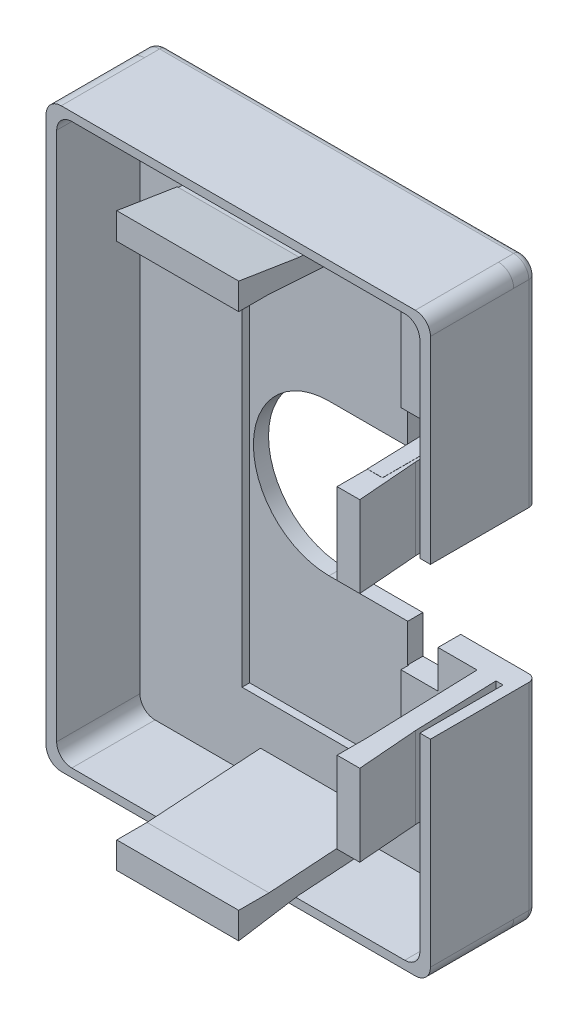
SolidWorks part; units mm, degrees
material "PLA"
ref_plane "Alzado" through (0, 0, 0) normal (0, 0, 1) x (1, 0, 0)
ref_plane "Planta" through (0, 0, 0) normal (0, 1, 0) x (1, 0, 0)
ref_plane "Vista lateral" through (0, 0, 0) normal (1, 0, 0) x (0, 0, -1)
sketch "Croquis1" plane through (0, 0, 0) normal (0, 0, 1) x (1, 0, 0)
  line L1 (25.4, 38.1) -> (-25.4, 38.1)
  line L2 (25.4, 38.1) -> (25.4, -38.1)
  line L3 (25.4, -38.1) -> (-25.4, -38.1)
  line L4 (-25.4, 38.1) -> (-25.4, -38.1)
  line L5 (25.4, 38.1) -> (-25.4, -38.1) construction
  line L6 (25.4, -38.1) -> (-25.4, 38.1) construction
  point P0 (0, 0)
  dimension "D1" = 76.2
  dimension "D2" = 50.8
extrude "Saliente-Extruir1" add sketch "Croquis1" along normal blind 18
sketch "Croquis2" plane through (0, 0, 18) normal (0, 0, 1) x (1, 0, 0)
  line L0 (25.4, 38.1) -> (-25.4, 38.1) construction
  line L1 (-23.06, 35.76) -> (23.06, 35.76)
  line L2 (-23.06, 35.76) -> (-23.06, -35.76)
  line L3 (-23.06, -35.76) -> (23.06, -35.76)
  line L4 (23.06, 35.76) -> (23.06, -35.76)
  line L5 (-25.4, -38.1) -> (25.4, -38.1) construction
  line L6 (-25.4, 38.1) -> (-25.4, -38.1) construction
  line L7 (25.4, -38.1) -> (25.4, 38.1) construction
  line L9 (-25.4, 38.1) -> (25.4, 38.1)
  line L10 (-25.4, 38.1) -> (-25.4, -38.1)
  line L11 (-25.4, -38.1) -> (25.4, -38.1)
  line L12 (25.4, 38.1) -> (25.4, -38.1)
  line L13 (-19.4, 32.1) -> (19.4, 32.1)
  line L14 (-19.4, 32.1) -> (-19.4, -32.1)
  line L15 (-19.4, -32.1) -> (19.4, -32.1)
  line L16 (19.4, 32.1) -> (19.4, -32.1)
  line M9 (-25.4, 38.1) -> (-25.4, -38.1)
  line M10 (-25.4, -38.1) -> (25.4, -38.1)
  line M11 (25.4, -38.1) -> (25.4, 38.1)
  line M12 (25.4, 38.1) -> (-25.4, 38.1)
  dimension "D1" = 2.34
  dimension "D2" = 2.34
  dimension "D3" = 2.34
  dimension "D4" = 2.34
  dimension "D5" = 6
  dimension "D6" = 6
  dimension "D7" = 6
  dimension "D8" = 6
extrude "Cortar-Extruir1" cut sketch "Croquis2" against normal blind 15 contours L1 L4 L3 L2 M12 M9 M10 M11 | L16 L13 L14 L15 region at (0, 37.1842, 18) region at (0, 0, 18)
sketch "Croquis3" plane through (0, 0, 18) normal (0, 0, 1) x (1, 0, 0)
  line L0 (-23.06, 35.76) -> (-23.06, -35.76) construction
  line L1 (-23.06, 22.1) -> (-19.4, 22.1)
  line L2 (-23.06, 22.1) -> (-23.06, -22.1)
  line L3 (-23.06, -22.1) -> (-19.4, -22.1)
  line L4 (-19.4, 22.1) -> (-19.4, -22.1)
  line L5 (-19.4, 32.1) -> (-19.4, -32.1) construction
  line L6 (-19.4, -32.1) -> (19.4, -32.1) construction
  line L7 (-9.4, -32.1) -> (9.3837, -32.1)
  line L8 (-9.4, -32.1) -> (-9.4, -35.76)
  line L9 (-9.4, -35.76) -> (9.3837, -35.76)
  line L10 (9.3837, -32.1) -> (9.3837, -35.76)
  line L11 (-23.06, -35.76) -> (23.06, -35.76) construction
  line L12 (19.4, 32.1) -> (19.4, -32.1) construction
  line L13 (19.4, -22.1) -> (23.06, -22.1)
  line L14 (19.4, -22.1) -> (19.4, 22.1)
  line L15 (19.4, 22.1) -> (23.06, 22.1)
  line L16 (23.06, -22.1) -> (23.06, 22.1)
  line L17 (23.06, 35.76) -> (23.06, -35.76) construction
  line L18 (-23.06, 35.76) -> (23.06, 35.76) construction
  line L19 (-9.4, 35.76) -> (9.4, 35.76)
  line L20 (-9.4, 35.76) -> (-9.4, 32.1)
  line L21 (-9.4, 32.1) -> (9.4, 32.1)
  line L22 (9.4, 35.76) -> (9.4, 32.1)
  line L23 (-19.4, 32.1) -> (19.4, 32.1) construction
  line L24 (-19.4, 32.1) -> (-19.4, -32.1) construction
  line L25 (19.4, 32.1) -> (19.4, -32.1) construction
  dimension "D1" = 10
  dimension "D2" = 10
  dimension "D3" = 10
  dimension "D4" = 10
  dimension "D5" = 10
  dimension "D6" = 10
  dimension "D7" = 10
extrude "Cortar-Extruir2" [suppressed] cut sketch "Croquis3" against normal blind 7
fillet "Redondeo1" [suppressed] radius 2
fillet "Redondeo2" [suppressed] radius 1
sketch "Croquis5" [suppressed] plane through (0, -38.1, 0) normal (0, -1, 0) x (1, 0, 0)
  line L0 (-23.4, 3) -> (23.4, 3) construction
  line L1 (-3, 3) -> (3, 3)
  line L2 (-3, 3) -> (-3, 1.5)
  line L3 (-3, 1.5) -> (3, 1.5)
  line L4 (3, 3) -> (3, 1.5)
  line L5 (0, 1) -> (0, 3) construction
  line L6 (-23.4, 1) -> (23.4, 1) construction
  dimension "D1" = 3
  dimension "D2" = 3
  dimension "D3" = 1.5
extrude "Cortar-Extruir4" [suppressed] cut sketch "Croquis5" against normal blind 6
sketch "Croquis6" plane through (0, 0, 18) normal (0, 0, 1) x (1, 0, 0)
  line L0 (-23.06, 35.76) -> (-8.06, 35.76)
  line L1 (-23.06, 35.76) -> (23.06, 35.76) construction
  line L2 (-8.06, 35.76) -> (-8.06, 32.1)
  line L3 (-19.4, 32.1) -> (19.4, 32.1) construction
  line L4 (-8.06, 32.1) -> (-19.4, 32.1)
  line L5 (-19.4, 32.1) -> (-19.4, 20.76)
  line L6 (-19.4, 32.1) -> (-19.4, -32.1) construction
  line L7 (-19.4, 20.76) -> (-23.06, 20.76)
  line L8 (-23.06, 35.76) -> (-23.06, -35.76) construction
  line L9 (-23.06, 20.76) -> (-23.06, 35.76)
  line L10 (23.06, 35.76) -> (8.06, 35.76)
  line L11 (-23.06, 35.76) -> (23.06, 35.76) construction
  line L12 (8.06, 35.76) -> (8.06, 32.1)
  line L13 (8.06, 32.1) -> (19.4, 32.1)
  line L14 (19.4, 32.1) -> (19.4, -32.1) construction
  line L15 (19.4, 32.1) -> (19.4, -32.1) construction
  line L16 (19.4, 32.1) -> (19.4, 20.76)
  line L17 (19.4, 20.76) -> (23.06, 20.76)
  line L18 (23.06, 35.76) -> (23.06, -35.76) construction
  line L19 (23.06, 20.76) -> (23.06, 35.76)
  line L20 (-23.06, -35.76) -> (-23.06, -20.76)
  line L21 (-23.06, 35.76) -> (-23.06, -35.76) construction
  line L22 (-23.06, -20.76) -> (-19.4, -20.76)
  line L23 (-19.4, 32.1) -> (-19.4, -32.1) construction
  line L24 (-19.4, -20.76) -> (-19.4, -32.1)
  line L25 (-19.4, -32.1) -> (-8.06, -32.1)
  line L26 (-19.4, -32.1) -> (19.4, -32.1) construction
  line L27 (-8.06, -32.1) -> (-8.06, -35.76)
  line L28 (-23.06, -35.76) -> (23.06, -35.76) construction
  line L29 (-8.06, -35.76) -> (-23.06, -35.76)
  line L30 (23.06, -35.76) -> (8.06, -35.76)
  line L31 (-23.06, -35.76) -> (23.06, -35.76) construction
  line L32 (8.06, -35.76) -> (8.06, -32.1)
  line L33 (-19.4, -32.1) -> (19.4, -32.1) construction
  line L34 (8.06, -32.1) -> (19.4, -32.1)
  line L35 (19.4, -32.1) -> (19.4, -20.76)
  line L36 (19.4, -20.76) -> (23.06, -20.76)
  line L37 (23.06, 35.76) -> (23.06, -35.76) construction
  line L38 (23.06, -20.76) -> (23.06, -35.76)
  dimension "D1" = 15
  dimension "D2" = 15
  dimension "D3" = 15
  dimension "D4" = 15
  dimension "D5" = 15
  dimension "D6" = 15
  dimension "D7" = 15
  dimension "D8" = 15
extrude "Cortar-Extruir8" cut sketch "Croquis6" against normal blind 15
sketch "Croquis10" plane through (0, -20.76, 0) normal (0, -1, 0) x (-1, 0, 0)
  line L0 (23.06, -18) -> (23.56, -18)
  line L1 (23.56, -18) -> (23.06, -3)
  line L2 (23.06, -3) -> (23.06, -18)
  line L3 (-23.06, -18) -> (-23.56, -18)
  line L4 (-23.56, -18) -> (-23.06, -3)
  line L5 (-23.06, -3) -> (-23.06, -18)
  dimension "D1" = 0.5
  dimension "D2" = 0.5
extrude "Saliente-Extruir3" add sketch "Croquis10" against normal blind 41.5
sketch "Croquis11" plane through (0, -20.76, 0) normal (0, -1, 0) x (1, 0, 0)
  line L0 (-19.4, 18) -> (-21.06, 18)
  line L1 (-19.4, 18) -> (-23.56, 18) construction
  line L2 (-21.06, 18) -> (-20.56, 3)
  line L3 (-19.4, 3) -> (-23.06, 3) construction
  line L4 (-20.56, 3) -> (-19.4, 3)
  line L5 (-19.4, 18) -> (-19.4, 3)
  dimension "D1" = 2.5
  dimension "D2" = 1.16
extrude "Cortar-Extruir9" cut sketch "Croquis11" against normal blind 51.5
sketch "Croquis12" plane through (0, -20.76, 0) normal (0, -1, 0) x (1, 0, 0)
  line L0 (19.4, 18) -> (19.4, 3)
  line L1 (19.4, 3) -> (20.56, 3)
  line L2 (23.06, 3) -> (19.4, 3) construction
  line L3 (20.56, 3) -> (21.06, 18)
  line L4 (23.56, 18) -> (19.4, 18) construction
  line L5 (21.06, 18) -> (19.4, 18)
  dimension "D1" = 2.5
  dimension "D2" = 1.16
extrude "Cortar-Extruir10" cut sketch "Croquis12" against normal blind 51.5
sketch "Croquis13" plane through (8.06, 0, 0) normal (1, 0, 0) x (0, 0, -1)
  line L0 (-18, -35.76) -> (-18, -36.76)
  line L1 (-18, -36.76) -> (-3, -35.76)
  line L2 (-3, -35.76) -> (-18, -35.76)
  line L3 (-18, 35.76) -> (-18, 36.76)
  line L4 (-18, 36.76) -> (-3, 35.76)
  line L5 (-3, 35.76) -> (-18, 35.76)
  dimension "D1" = 1
  dimension "D2" = 1
extrude "Saliente-Extruir4" add sketch "Croquis13" against normal blind 16
sketch "Croquis14" plane through (8.06, 0, 0) normal (1, 0, 0) x (0, 0, -1)
  line L0 (-3, -32.1) -> (-18, -32.1)
  line L1 (-18, -32.1) -> (-18, -34.26)
  line L2 (-18, -32.1) -> (-18, -36.76) construction
  line L3 (-18, -34.26) -> (-3, -33.26)
  line L4 (-3, -32.1) -> (-3, -35.76) construction
  line L5 (-3, -33.26) -> (-3, -32.1)
  line L6 (-18, 32.1) -> (-18, 34.26)
  line L7 (-18, 36.76) -> (-18, 32.1) construction
  line L8 (-18, 34.26) -> (-3, 33.26)
  line L9 (-3, 35.76) -> (-3, 32.1) construction
  line L10 (-3, 33.26) -> (-3, 32.1)
  line L11 (-3, 32.1) -> (-18, 32.1)
  dimension "D1" = 2.5
  dimension "D2" = 1.16
  dimension "D3" = 2.5
  dimension "D4" = 1.16
extrude "Cortar-Extruir11" cut sketch "Croquis14" against normal blind 16.5
fillet "Redondeo3" radius 2 4 edges at (25.4, 38.1, 1.5) (-25.4, 38.1, 1.5) (-25.4, -38.1, 1.5) (25.4, -38.1, 1.5)
fillet "Redondeo4" radius 1 8 edges at (-24.8142, 37.5142, 0) (-25.4, 0, 0) (-24.8142, -37.5142, 0) (0, -38.1, 0) (24.8142, -37.5142, 0) (25.4, 0, 0) (24.8142, 37.5142, 0) (0, 38.1, 0)
sketch "Croquis15" plane through (0, 0, 18) normal (0, 0, 1) x (1, 0, 0)
  line L0 (-23.56, -0.01) -> (23.56, -0.01) construction
  line L1 (-23.56, 20.74) -> (-23.56, -20.76) construction
  line L2 (23.56, 20.74) -> (23.56, -20.76) construction
  line L4 (-23.56, 4.99) -> (23.56, 4.99)
  line L5 (-23.56, 4.99) -> (-23.56, -5.01)
  line L6 (-23.56, -5.01) -> (23.56, -5.01)
  line L7 (23.56, 4.99) -> (23.56, -5.01)
  dimension "D1" = 5
  dimension "D2" = 5
extrude "Cortar-Extruir12" cut sketch "Croquis15" against normal blind 15
sketch "Croquis16" plane through (0, -38.1, 0) normal (0, -1, 0) x (1, 0, 0)
  line L0 (-23.4, 3) -> (23.4, 3) construction
  line L1 (-4, 3) -> (4, 3)
  line L2 (-4, 3) -> (-4, 1.5)
  line L3 (-4, 1.5) -> (4, 1.5)
  line L4 (4, 3) -> (4, 1.5)
  dimension "D1" = 1.5
  dimension "D2" = 8
  dimension "D3" = 4
extrude "Cortar-Extruir13" [suppressed] cut sketch "Croquis16" against normal blind 2
sketch "Croquis17" plane through (0, 0, 3) normal (0, 0, 1) x (1, 0, 0)
  line L0 (-25.4, 36.1) -> (-25.4, -36.1) construction
  line L1 (-23.4, -38.1) -> (23.4, -38.1) construction
  circle A0 centre (-13.4, -23.1) radius 3
  dimension "D2" = 6
  dimension "D1" = 12
  dimension "D3" = 15
extrude "Cortar-Extruir14" [suppressed] cut sketch "Croquis17" against normal blind 10
sketch "Croquis18" plane through (0, 0, 3) normal (0, 0, 1) x (1, 0, 0)
  line L0 (0, 10) -> (25.4, 10)
  line L1 (25.4, -36.1) -> (25.4, 36.1) construction
  line L2 (0, -10) -> (25.4, -10)
  line L3 (25.4, -10) -> (25.4, 10)
  circle A0 centre (0, 0) radius 10
  line M7 (25.4, -36.1) -> (25.4, 36.1)
  line M14 (23.06, 20.74) -> (23.06, 4.99)
  line M15 (23.06, 4.99) -> (20.56, 4.99)
  line M16 (20.56, 4.99) -> (20.56, 20.76)
  line M28 (20.56, -20.76) -> (20.56, -5.01)
  line M29 (20.56, -5.01) -> (23.06, -5.01)
  line M30 (23.06, -5.01) -> (23.06, -20.76)
  dimension "D1" = 20
extrude "Cortar-Extruir16" cut sketch "Croquis18" against normal through all and the other way through all contours A0 | L2 M28 M30 M29 | L0 M16 M15 M14 | A0 L2 L0 M28 M29 M30 M7 M14 M15 M16 region at (16.0766, -0.0008, 3) region at (0, 0, 3) region at (21.81, 7.495, 3) region at (21.81, -7.505, 3)
sketch "Croquis19" plane through (0, 0, 3) normal (0, 0, 1) x (1, 0, 0)
  line L0 (0, 10) -> (20.56, 10) construction
  line L1 (10.4, 10) -> (15.4, 10)
  line L2 (10.4, 10) -> (10.4, 15)
  line L3 (10.4, 15) -> (15.4, 15)
  line L4 (15.4, 10) -> (15.4, 15)
  line L5 (0, -10) -> (20.56, -10) construction
  line L6 (10.4, -10) -> (15.4, -10)
  line L7 (10.4, -10) -> (10.4, -15)
  line L8 (10.4, -15) -> (15.4, -15)
  line L9 (15.4, -10) -> (15.4, -15)
  dimension "D1" = 5
  dimension "D2" = 5
  dimension "D3" = 5
  dimension "D4" = 5
  dimension "D5" = 10
  dimension "D6" = 10
extrude "Cortar-Extruir17" cut sketch "Croquis19" against normal through all
sketch "Croquis20" plane through (0, 0, 3) normal (0, 0, 1) x (1, 0, 0)
  line L1 (-25.4, 38.1) -> (25.4, 38.1)
  line L2 (-25.4, 38.1) -> (-25.4, -38.1)
  line L3 (-25.4, -38.1) -> (25.4, -38.1)
  line L4 (25.4, 38.1) -> (25.4, -38.1)
  line L5 (-25.4, 38.1) -> (25.4, -38.1) construction
  line L6 (-25.4, -38.1) -> (25.4, 38.1) construction
  line L7 (24, 37) -> (-24, 37)
  line L8 (24, 37) -> (24, -37)
  line L9 (24, -37) -> (-24, -37)
  line L10 (-24, 37) -> (-24, -37)
  line L11 (24, 37) -> (-24, -37) construction
  line L12 (24, -37) -> (-24, 37) construction
  point P0 (0, 0)
  point P6 (0, 0)
  dimension "D1" = 76.2
  dimension "D2" = 50.8
  dimension "D3" = 48
  dimension "D4" = 74
extrude "Saliente-Extruir5" add sketch "Croquis20" along normal blind 11 contours L2 L1 L4 L3 | L8 L7 L10 L9
sketch "Croquis21" plane through (25.4, 0, 0) normal (1, 0, 0) x (0, 0, -1)
  line L1 (-3, 10) -> (-28, 10)
  line L2 (-3, 10) -> (-3, -10)
  line L3 (-3, -10) -> (-28, -10)
  line L4 (-28, 10) -> (-28, -10)
  dimension "D1" = 20
  dimension "D2" = 25
extrude "Cortar-Extruir18" cut sketch "Croquis21" against normal blind 10
sketch "Croquis22" plane through (0, 0, 3) normal (0, 0, 1) x (1, 0, 0)
  line L1 (10.5, 27.5) -> (-10.5, 27.5)
  line L2 (10.5, 27.5) -> (10.5, -27.5)
  line L3 (10.5, -27.5) -> (-10.5, -27.5)
  line L4 (-10.5, 27.5) -> (-10.5, -27.5)
  line L5 (10.5, 27.5) -> (-10.5, -27.5) construction
  line L6 (10.5, -27.5) -> (-10.5, 27.5) construction
  point P0 (0, 0)
  dimension "D1" = 21
  dimension "D2" = 55
extrude "Cortar-Extruir19" cut sketch "Croquis22" against normal blind 1
fillet "Redondeo5" radius 2 8 edges at (25.4, -38.1, 8.5) (-25.4, -38.1, 8.5) (-25.4, 38.1, 8.5) (25.4, 38.1, 8.5) (-24, 37, 8.5) (-24, -37, 8.5) (24, -37, 8.5) (24, 37, 8.5)
sketch "Croquis23" plane through (0, 0, 18) normal (0, 0, 1) x (1, 0, 0)
  line L0 (-23.56, 20.74) -> (-23.56, 4.99) construction
  line L5 (-21.06, 20.76) -> (-23.56, 20.76)
  line L6 (-21.06, 20.76) -> (-21.06, 5.0051)
  line L7 (-21.06, 5.0051) -> (-23.56, 5.0051)
  line L8 (-23.56, 20.76) -> (-23.56, 5.0051)
  line L9 (-23.56, -5.01) -> (-23.56, -20.76) construction
  line L10 (-21.06, -5.01) -> (-23.56, -5.01)
  line L11 (-21.06, -5.01) -> (-21.06, -20.76)
  line L12 (-21.06, -20.76) -> (-23.56, -20.76)
  line L13 (-23.56, -5.01) -> (-23.56, -20.76)
  line L32 (23.56, 20.74) -> (21.06, 20.74)
  line L33 (23.56, 20.74) -> (23.56, 10)
  line L34 (23.56, 10) -> (21.06, 10)
  line L35 (21.06, 20.74) -> (21.06, 10)
  line L45 (8.06, 34.26) -> (-8.0656, 34.26)
  line L46 (8.06, 34.26) -> (8.06, 36.7624)
  line L47 (8.06, 36.7624) -> (-8.0656, 36.7624)
  line L48 (-8.0656, 34.26) -> (-8.0656, 36.7624)
  line L49 (-8.06, -34.26) -> (8.06, -34.26)
  line L50 (-8.06, -34.26) -> (-8.06, -36.76)
  line L51 (-8.06, -36.76) -> (8.06, -36.76)
  line L52 (8.06, -34.26) -> (8.06, -36.76)
  line L53 (23.56, -10) -> (21.06, -10)
  line L54 (23.56, -10) -> (23.56, -20.76)
  line L55 (23.56, -20.76) -> (21.06, -20.76)
  line L56 (21.06, -10) -> (21.06, -20.76)
extrude "Saliente-Extruir6" add sketch "Croquis23" along normal blind 4
sketch "Croquis24" plane through (0, 0, 22) normal (0, 0, 1) x (1, 0, 0)
  line L1 (-23.56, 20.76) -> (-20.56, 20.76)
  line L2 (-23.56, 20.76) -> (-23.56, 4.99)
  line L3 (-23.56, 4.99) -> (-20.56, 4.99)
  line L4 (-20.56, 20.76) -> (-20.56, 4.99)
  line L5 (-23.56, -5.01) -> (-20.56, -5.01)
  line L6 (-23.56, -5.01) -> (-23.56, -20.76)
  line L7 (-23.56, -20.76) -> (-20.56, -20.76)
  line L8 (-20.56, -5.01) -> (-20.56, -20.76)
extrude "Cortar-Extruir20" cut sketch "Croquis24" against normal blind 19
sketch "Croquis25" plane through (0, 20.74, 0) normal (0, 1, 0) x (1, 0, 0)
  line L0 (23.56, -22) -> (24.06, -22)
  line L1 (24.06, -22) -> (23.4267, -14)
  line L2 (23.06, -3) -> (23.56, -18) construction
  line L3 (23.56, -22) -> (23.4267, -14)
  dimension "D1" = 0.5
  dimension "D2" = 8
extrude "Saliente-Extruir7" add sketch "Croquis25" against normal up to surface (10.74 mm away) up to face at (22.0821, 10, 9.2918)
sketch "Croquis26" plane through (0, -20.76, 0) normal (0, -1, 0) x (1, 0, 0)
  line L0 (23.56, 22) -> (23.4267, 14)
  line L1 (23.06, 3) -> (23.56, 18) construction
  line L2 (23.4267, 14) -> (24.06, 22)
  line L3 (24.06, 22) -> (23.56, 22)
  dimension "D1" = 8
extrude "Saliente-Extruir8" add sketch "Croquis26" against normal up to surface (10.76 mm away) up to face at (22.0821, -10, 9.2918)
sketch "Croquis27" plane through (8.06, 0, 0) normal (1, 0, 0) x (0, 0, -1)
  line L0 (-22, 36.7624) -> (-22, 37.7624)
  line L1 (-22, 37.7624) -> (-14, 36.4942)
  line L2 (-3, 35.76) -> (-18, 36.7612) construction
  line L3 (-14, 36.4942) -> (-22, 36.4942)
  line L4 (-22, 34.26) -> (-22, 36.7624) construction
  line L5 (-22, 36.4942) -> (-22, 36.7624)
  dimension "D1" = 8
  dimension "D2" = 1
extrude "Saliente-Extruir9" add sketch "Croquis27" against normal up to surface (16.1256 mm away) up to face at (-8.065, 35.5112, 20.4)
sketch "Croquis28" plane through (8.06, 0, 0) normal (1, 0, 0) x (0, 0, -1)
  line L0 (-22, -36.76) -> (-22, -37.76)
  line L1 (-22, -37.76) -> (-14, -36.49)
  line L2 (-14, -36.49) -> (-22, -36.49)
  line L3 (-22, -36.76) -> (-22, -34.26) construction
  line L4 (-22, -36.49) -> (-22, -36.76)
  dimension "D1" = 1
  dimension "D2" = 8
  dimension "D3" = 0.27
extrude "Saliente-Extruir10" add sketch "Croquis28" against normal up to surface (16.12 mm away) up to face at (-8.06, -35.26, 14.8571)
ref_plane "Plano1" [suppressed] through (0, 0, 0) normal (-1, 0, 0) x (0, 0, 1)
sketch "Croquis29" [suppressed] plane through (0, 0, 0) normal (-1, 0, 0) x (0, 0, 1)
  line L0 (0, -36.1) -> (0, 36.1) construction
  line L1 (11, 34.1) -> (3, 30.1)
  line L2 (3, 30.1) -> (3, 34.1)
  line L3 (3, 34.1) -> (11, 34.1)
  line L4 (3, 34.1) -> (0, 34.1) construction
  line L5 (3, 38.1) -> (14, 38.1) construction
  line L6 (3, -34.1) -> (11, -34.1)
  line L7 (11, -34.1) -> (3, -30.1)
  line L8 (3, -30.1) -> (3, -34.1)
  line L9 (14, -38.1) -> (3, -38.1) construction
  dimension "D1" = 4
  dimension "D2" = 8
  dimension "D3" = 3
  dimension "D4" = 4
  dimension "D5" = 4
  dimension "D6" = 8
  dimension "D7" = 4
  dimension "D8" = 3
extrude "Saliente-Extruir11" [suppressed] add sketch "Croquis29" along normal blind 3 and the other way blind 3
